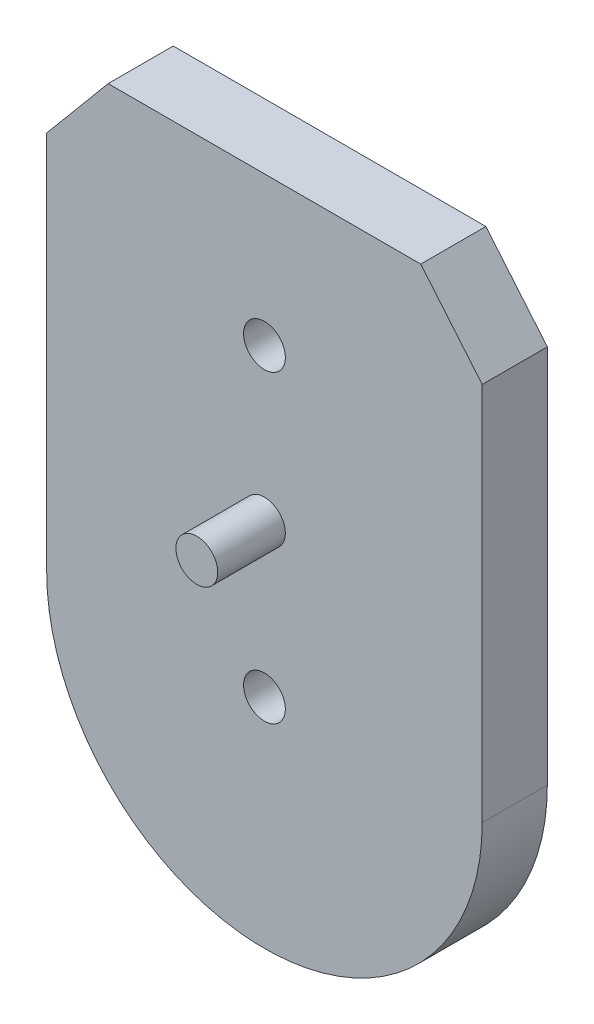
SolidWorks part; units mm, degrees
ref_plane "Front Plane" through (0, 0, 0) normal (0, 0, 1) x (1, 0, 0)
ref_plane "Top Plane" through (0, 0, 0) normal (0, 1, 0) x (1, 0, 0)
ref_plane "Right Plane" through (0, 0, 0) normal (1, 0, 0) x (0, 0, -1)
sketch "Sketch1" plane through (0, 0, 0) normal (0, 0, 1) x (1, 0, 0)
  line L2 (125, 80.4995) -> (125, -137.375)
  line L4 (-125, 80.5) -> (-125, -137.375)
  line L8 (-125, 80.4995) -> (-89.7236, 122.7033)
  line L9 (89.7236, 122.7033) -> (125, 80.4995)
  line L12 (-89.7236, 122.7033) -> (89.7236, 122.7033)
  circle A0 centre (0, 37.375) radius 28.75
  circle A1 centre (0, 37.375) radius 12
  circle A2 centre (0, -137.375) radius 12
  circle A3 centre (0, -137.375) radius 28.75
  circle A6 centre (0, -50) radius 12
  circle A7 centre (0, -50) radius 30
  arc A12 (-125, -137.375) -> (125, -137.375) centre (0, -137.375) ccw
  point P0 (0, 0)
  dimension "D3" = 24
  dimension "D4" = 57.5
  dimension "D5" = 24
  dimension "D6" = 57.5
  dimension "D8" = 60
  dimension "D9" = 24
  dimension "D12" = 250
  dimension "D2" = 217.875
  dimension "D7" = 87.375
  dimension "D10" = 37.375
  dimension "D11" = 174.75
extrude "Boss-Extrude1" add sketch "Sketch1" along normal mid plane 37.375 contours L4 A12 L2 A0 A3 A7 | A0 A1 | A7 A6 | A3 A2 | A6 region at (120.4089, -28.4377, 0) region at (-27.9368, 37.375, 0) region at (-27.9368, -137.375, 0) region at (0, -50, 0) region at (-29.1515, -50, 0)
extrude "Boss-Extrude2" add sketch "Sketch1<4>" along normal blind 57.5 contours A6
sketch "Sketch1<4>" plane through (0, 0, 0) normal (0, 0, 1) x (1, 0, 0) same geometry as "Sketch1"
